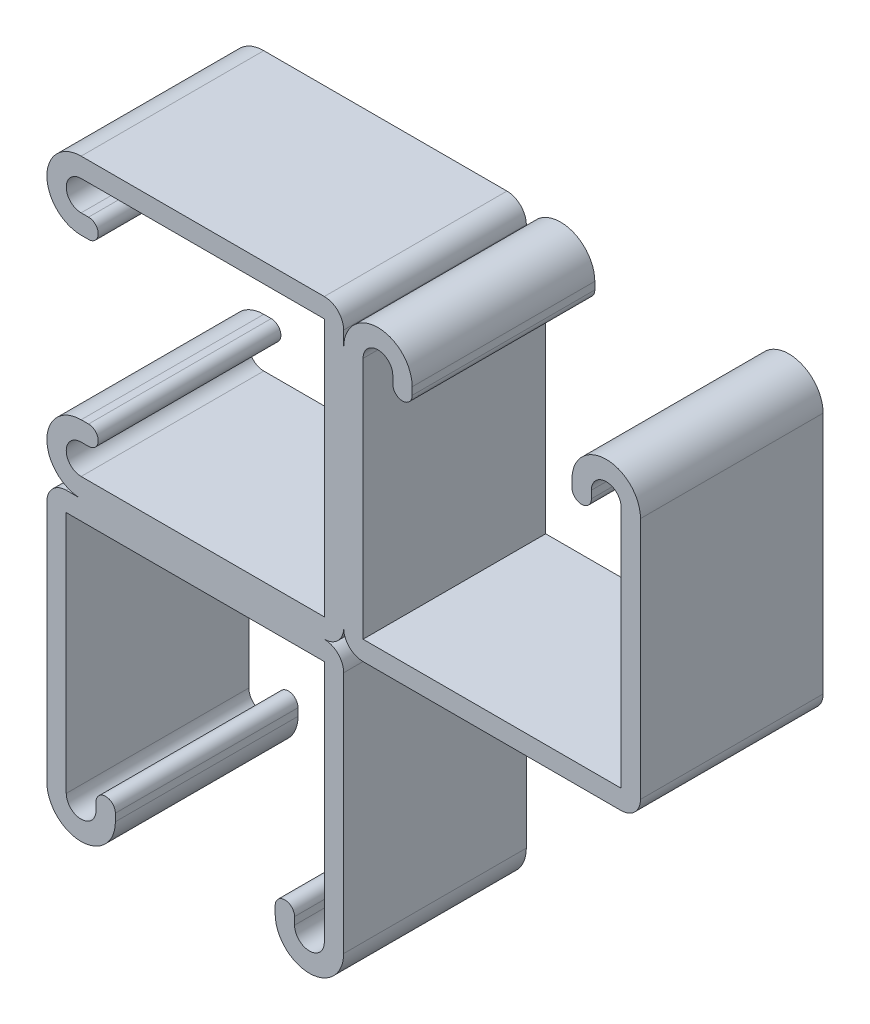
SolidWorks part; units mm, degrees
note: '?' marks a value the reader was unsure of.
ref_plane "Plane1" through (0, 0, 0) normal (0, 0, 1) x (1, 0, 0)
ref_plane "Plane2" through (0, 0, 0) normal (0, 1, 0) x (1, 0, 0)
ref_plane "Plane3" through (0, 0, 0) normal (1, 0, 0) x (0, 0, -1)
sketch "Sketch1" plane through (0, 0, 0) normal (0, 0, 1) x (1, 0, 0)
  line L0 (0, 36.5125) -> (0, 2.6924)
  line L1 (2.6924, 0) -> (38.5826, 0)
  line L2 (41.275, 2.6924) -> (41.275, 36.5125)
  line L3 (31.75, 36.5125) -> (31.75, 35.4774)
  line L4 (9.525, 36.5125) -> (9.525, 35.4774)
  line L5 (6.8326, 36.5125) -> (6.8326, 35.4774)
  line L6 (2.6924, 36.5125) -> (2.6924, 2.6924)
  line L7 (2.6924, 2.6924) -> (38.5826, 2.6924)
  line L8 (38.5826, 2.6924) -> (38.5826, 36.5125)
  line L9 (34.4424, 36.5125) -> (34.4424, 35.4774)
  line L10 (-4.7625, 41.275) -> (46.0375, 41.275) construction
  line L11 (7.7851, 34.1313) -> (33.4899, 34.1313) construction
  arc A0 (41.275, 36.5125) -> (31.75, 36.5125) centre (36.5125, 36.5125) ccw
  arc A1 (0, 36.5125) -> (9.525, 36.5125) centre (4.7625, 36.5125) cw
  arc A2 (2.6924, 0) -> (0, 2.6924) centre (2.6924, 2.6924) cw
  arc A3 (38.5826, 0) -> (41.275, 2.6924) centre (38.5826, 2.6924) ccw
  arc A4 (2.6924, 36.5125) -> (6.8326, 36.5125) centre (4.7625, 36.5125) cw
  arc A5 (38.5826, 36.5125) -> (34.4424, 36.5125) centre (36.5125, 36.5125) ccw
  arc A6 (31.75, 35.4774) -> (34.4424, 35.4774) centre (33.0962, 35.4774) ccw
  arc A7 (9.525, 35.4774) -> (6.8326, 35.4774) centre (8.1788, 35.4774) cw
  dimension "D6" = 9.525
  dimension "D7" = 22.225
  dimension "D9" = 7.1437
  dimension "D2" = 41.275
extrude "Base-Extrude" add sketch "Sketch1" along normal mid plane 25.4
ref_axis "Axis1" through (0, 0, -50) along (0, 0, 1)?
pattern_circular "CirPattern1" count 3 every 90 about axis through (0, 0, 0) along (0, 0, 1) of "Base-Extrude"
equation "\"D7@Sketch1\" = \"Width@Sketch1\" - 2 * \"D6@Sketch1\""
equation "\"D1@Sketch1\" = \"gauge@Sketch1\""
